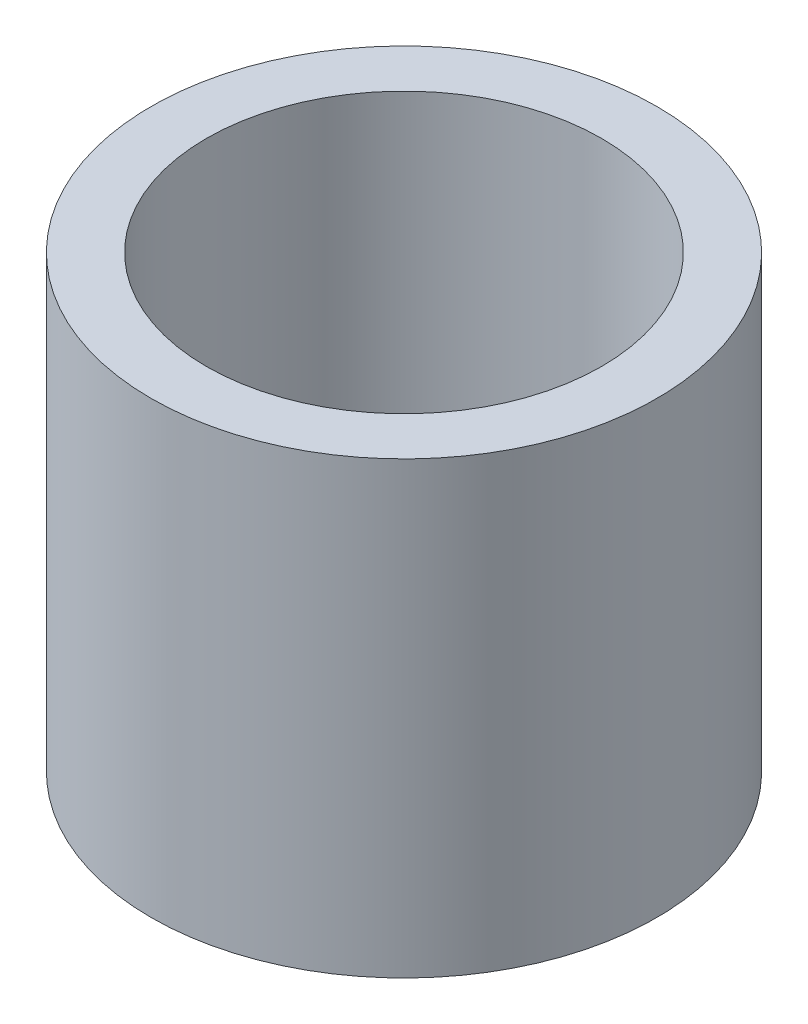
SolidWorks part; units mm, degrees
material "Brass"
ref_plane "Front Plane" through (0, 0, 0) normal (0, 0, 1) x (1, 0, 0)
ref_plane "Top Plane" through (0, 0, 0) normal (0, 1, 0) x (1, 0, 0)
ref_plane "Right Plane" through (0, 0, 0) normal (1, 0, 0) x (0, 0, -1)
sketch "Sketch1" plane through (0, 0, 0) normal (0, 1, 0) x (1, 0, 0)
  circle A0 centre (0, 0) radius 5.5816
  circle A1 centre (0, 0) radius 7.1438
  dimension "D1" = 11.1633
  dimension "D2" = 14.2875
extrude "Boss-Extrude1" add sketch "Sketch1" along normal blind 12.7
